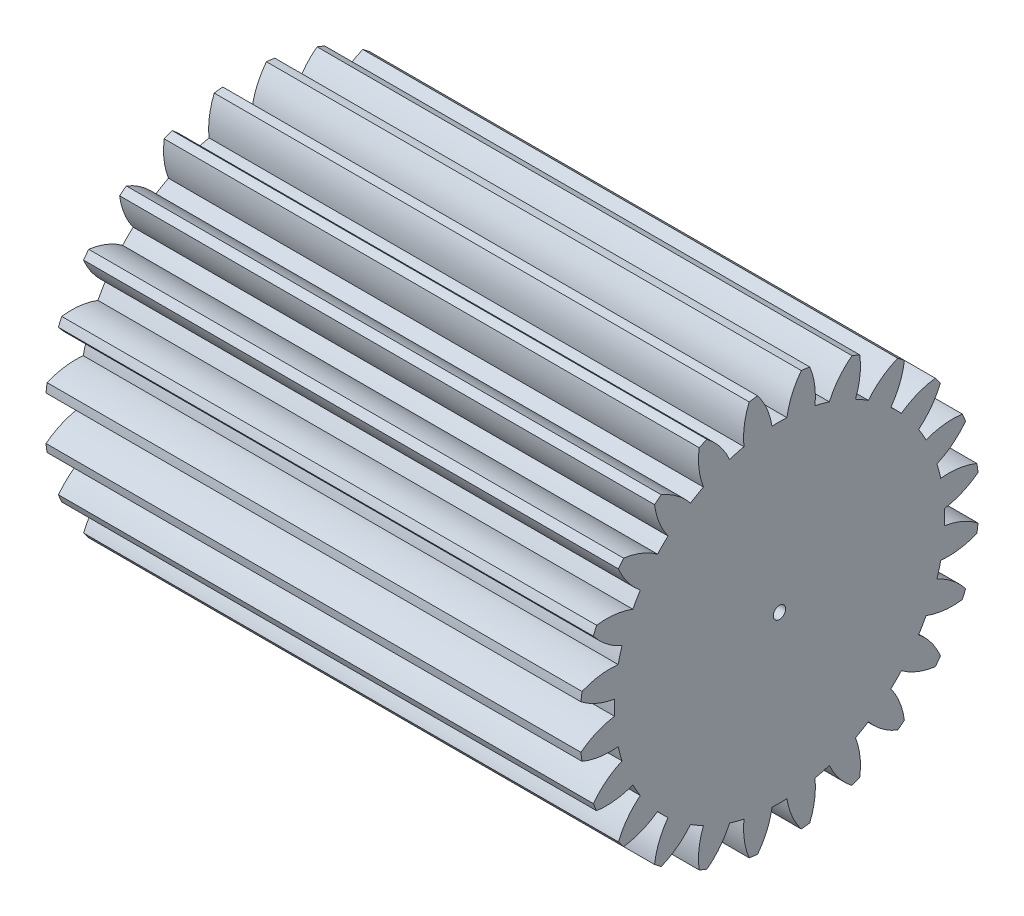
SolidWorks part; units mm, degrees
ref_plane "Plane1" through (0, 0, 0) normal (0, 0, 1) x (1, 0, 0)
ref_plane "Plane2" through (0, 0, 0) normal (0, 1, 0) x (1, 0, 0)
ref_plane "Plane3" through (0, 0, 0) normal (1, 0, 0) x (0, 0, -1)
sketch "HoldingSke" plane through (0, 0, 0) normal (0, 1, 0) x (1, 0, 0)
  line L0 (0, 0) -> (0.9135, -0.4067)
  line L1 (-15, 0) -> (100, 0) construction
  line L2 (0, 0) -> (-2.1039, 2.3779)
  line L3 (0, 0) -> (-11.863, 4.5341)
  line L4 (0, 0) -> (7.8894, 3.5126)
  line L5 (0, 0) -> (-46.8476, -17.4728)
  line L6 (0, 0) -> (-9.9476, -6.7116)
  line L7 (-2.1039, 2.3779) -> (8.6586, 51.2059)
  line L8 (-76.2, 54.61) -> (-76.1, 54.61)
  line L9 (-71.009, 38.7566) -> (-53.1078, 45.2721)
  line L10 (-76.2, 71.12) -> (104.1128, 71.12)
  line L11 (0, 0) -> (-12, 0)
  line L12 (-76.2, 101.6) -> (-76.162, 101.6)
  line L13 (24.9733, 27.94) -> (52.9518, 28.4284)
  line L14 (24.9733, 27.94) -> (24.9743, 27.94)
  line L15 (24.9733, 27.94) -> (100.4006, 29.5858)
  line L16 (-63.627, -1) -> (-12.827, -1)
  circle A0 centre (0, 0) radius 0.4
  circle A1 centre (0, 0) radius 10.749
  circle A2 centre (0, 0) radius 37.5
  circle A3 centre (0, 0) radius 0.4
  dimension "Num_teeth" = 24
  dimension "Pitch_radius" = 180.3128
  dimension "Width" = 12
sketch "BasProSke" plane through (0, 0, 0) normal (0, 1, 0) x (1, 0, 0)
  line L0 (-10, 0) -> (60, 0) construction
  line L1 (0, 0) -> (0, 13)
  line L2 (0, 0) -> (34.815, 0)
  line L3 (34.815, 0) -> (34.815, 13)
  line L4 (34.815, 13) -> (0, 13)
  dimension "Thickness" = 34.815
  dimension "Diameter" = 26
revolve "Base-Revolve" add sketch "BasProSke" angle 360 about L0
sketch "TooCutSke" plane through (0, 0, 0) normal (1, 0, 0) x (0, 0, -1)
  line L1 (0, 0) -> (0, 107) construction
  line L2 (0, 0) -> (-0.8513, 11.9698) construction
  line L3 (0, 0) -> (-3.127, 23.752) construction
  line L4 (-0.8513, 11.9698) -> (-1.5635, 11.876) construction
  arc A0 (0.4834, 10.7381) -> (-0.4834, 10.7381) centre (0, 0) ccw
  arc A1 (1.4409, 12.9455) -> (-1.4409, 12.9455) centre (0, 0) ccw
  circle A2 centre (0, 0) radius 12 construction
  circle A3 centre (0, 0) radius 11.2763 construction
  arc A4 (-0.4834, 10.7381) -> (-1.4409, 12.9455) centre (-5.2252, 9.9926) ccw
  arc A5 (1.4409, 12.9455) -> (0.4834, 10.7381) centre (5.2252, 9.9926) ccw
extrude "ToothCut" cut sketch "TooCutSke" along normal through all
fillet "Breaks" [suppressed] radius 0.02 tangent propagation no
fillet "RootFillets" [suppressed] radius 0.251
pattern_circular "TeethCuts" count 24 every 15 about axis through (-10, 0, 0) along (1, 0, 0) of "ToothCut", "RootFillets", "Breaks"
sketch "HubNeaOneSke" plane through (0, 0, 0) normal (-1, 0, 0) x (0, 0, 1)
  circle A0 centre (0, 0) radius 10.749
  dimension "Diameter" = 21.498
extrude "HubNearOne" [suppressed] add sketch "HubNeaOneSke" along normal blind 15.1851
sketch "HubNeaBotSke" plane through (0, 0, 0) normal (-1, 0, 0) x (0, 0, 1)
  circle A0 centre (0, 0) radius 10.749
  dimension "Diameter" = 21.498
extrude "HubNearBoth" [suppressed] add sketch "HubNeaBotSke" along normal blind 7.5925
ref_plane "FarPln" through (34.815, 0, 0) normal (1, 0, 0) x (0, 0, -1)
sketch "HubFarSke" plane through (34.815, 0, 0) normal (1, 0, 0) x (0, 0, -1)
  circle A0 centre (0, 0) radius 10.749
  dimension "Diameter" = 21.498
extrude "HubFar" [suppressed] add sketch "HubFarSke" along normal blind 7.5925
sketch "BorSke" plane through (0, 0, 0) normal (1, 0, 0) x (0, 0, -1)
  circle A0 centre (0, 0) radius 0.4
  dimension "Diameter" = 0.8
extrude "Bore" cut sketch "BorSke" along normal mid plane 100.0001
sketch "KeySke" plane through (0, 0, 0) normal (1, 0, 0) x (0, 0, -1)
  line L0 (-0.05, 0) -> (-0.05, 0.5)
  line L1 (-0.05, 0.5) -> (0.05, 0.5)
  line L2 (0.05, 0.5) -> (0.05, 0)
  line L3 (0, 0) -> (0, 34) construction
  line L4 (-0.05, 0) -> (0.05, 0)
  dimension "Width" = 0.1
extrude "Keyway" [suppressed] cut sketch "KeySke" along normal mid plane 100.0001
pattern_circular "Keyway2" [suppressed] count 2 every 90 about axis through (-10, 0, 0) along (1, 0, 0) reverse direction yes
scale "Scale1" scale about centroid uniform scaling yes scale factor 2
sketch "Sketch1" plane through (52.2225, 0, 0) normal (1, 0, 0) x (0, 0, -1)
  circle A0 centre (0, 0) radius 23.749 construction
  dimension "D1" = 47.498
equation "' \"Module@HoldingSke\" = 6.35"
equation "' \"Num_teeth@HoldingSke\" = 12"
equation "' \"Ap@HoldingSke\" =  20"
equation "' \"Ap@HoldingSke\" = 20"
equation "' \"Width@HoldingSke\" = 0.5 * 25.4"
equation "' \"Hub_dia@HoldingSke\"= 1 * 25.4"
equation "' \"Hub_dia@HoldingSke\" = 1 * 25.4"
equation "' \"Overall_len@HoldingSke\" = 1.0 * 25.4"
equation "' \"Bore@HoldingSke\" = 0.75 * 25.4"
equation "' \"T_dim@HoldingSke\" = 0.1 * 25.4"
equation "' \"Width@KeySke\" = 0.25 * 25.4"
equation "' \"Show_teeth@HoldingSke\" = 13"
equation "' \"Backlash@HoldingSke\" = 0.009 * 25.4"
equation "' \"Addendum_fac@HoldingSke\" = 1.0"
equation "' \"Dedendum_fac@HoldingSke\" = 1.25"
equation "' \"Dedendum_add@HoldingSke\" = 0.00005 * 25.4"
equation "' \"Clearance_fac@HoldingSke\" = 0.25"
equation "\"Pitch@HoldingSke\" = 1 / \"Module@HoldingSke\""
equation "\"Overcut_dia@TooCutSke\" = (\"Num_teeth@HoldingSke\" + 2 * \"Addendum_fac@HoldingSke\") / \"Pitch@HoldingSke\" + 0.002 * 25.4"
equation "\"Pitch_dia@TooCutSke\" = \"Num_teeth@HoldingSke\" / \"Pitch@HoldingSke\""
equation "\"Base_dia@TooCutSke\" = \"Num_teeth@HoldingSke\" / \"Pitch@HoldingSke\" * cos((\"Ap@HoldingSke\"  * 3.14159265 / 180))"
equation "\"Root_dia@TooCutSke\" = (\"Num_teeth@HoldingSke\" + 2) / \"Pitch@HoldingSke\" - 2 * (\"Addendum_fac@HoldingSke\" + \"Dedendum_fac@HoldingSke\") / \"Pitch@HoldingSke\" - \"Dedendum_add@HoldingSke\" * 2"
equation "\"Half_ang@TooCutSke\" = 180 / \"Num_teeth@HoldingSke\""
equation "\"Half_CT@TooCutSke\" = \"Num_teeth@HoldingSke\" / \"Pitch@HoldingSke\" * sin((3.14159265 / 2 / \"Num_teeth@HoldingSke\")) / 2 - 7 * \"Backlash@HoldingSke\" / 4"
equation "\"Flank_rad@TooCutSke\" = \"Num_teeth@HoldingSke\" / \"Pitch@HoldingSke\" / 5"
equation "\"Radius@RootFillets\" = \"Clearance_fac@HoldingSke\" / \"Pitch@HoldingSke\" + \"Dedendum_add@HoldingSke\""
equation "\"Break_rad@Breaks\" = 0.02 / \"Pitch@HoldingSke\""
equation "\"Thickness@HoldingSke\" = \"Width@HoldingSke\""
equation "\"OAL@HoldingSke\" = \"Thickness@HoldingSke\""
equation "\"MHD@HoldingSke\" = (\"Num_teeth@HoldingSke\" + 2) / \"Pitch@HoldingSke\" - 2 * (\"Addendum_fac@HoldingSke\" + \"Dedendum_fac@HoldingSke\")  / \"Pitch@HoldingSke\" - \"Dedendum_add@HoldingSke\" * 2"
equation "\"MBD@HoldingSke\" = (\"Num_teeth@HoldingSke\" + 2) / \"Pitch@HoldingSke\" - 2 * (\"Addendum_fac@HoldingSke\" + \"Dedendum_fac@HoldingSke\")  / \"Pitch@HoldingSke\" - \"Dedendum_add@HoldingSke\" * 2 - 0.002 * 25.4"
equation "\"MHD@HoldingSke\" = ((sgn( \"MHD@HoldingSke\" - \"Hub_dia@HoldingSke\" )-1)*( \"MHD@HoldingSke\" - \"Hub_dia@HoldingSke\" ))/-2+ \"Hub_dia@HoldingSke\""
equation "\"MBD@HoldingSke\" = ((sgn( \"MBD@HoldingSke\" - \"Bore@HoldingSke\" )-1)*( \"MBD@HoldingSke\" - \"Bore@HoldingSke\" ))/-2+ \"Bore@HoldingSke\""
equation "\"OAL@HoldingSke\" = ((sgn( \"OAL@HoldingSke\" - \"Overall_len@HoldingSke\" )+1)*( \"OAL@HoldingSke\" - \"Overall_len@HoldingSke\" ))/2 + \"Overall_len@HoldingSke\" + 0.000002 * 25.4"
equation "\"Num_teeth@TeethCuts\" = int( \"Show_teeth@HoldingSke\" ) + 1"
equation "\"Num_teeth@TeethCuts\" = ((sgn( \"Num_teeth@TeethCuts\" - \"Num_teeth@HoldingSke\" )-1)*( \"Num_teeth@TeethCuts\" - \"Num_teeth@HoldingSke\" ))/-2+ \"Num_teeth@HoldingSke\""
equation "\"Num_teeth@TeethCuts\" = ((sgn( \"Num_teeth@TeethCuts\" - 2.0)+1)*( \"Num_teeth@TeethCuts\" - 2.0))/2 +2.0"
equation "\"Angle@TeethCuts\" = 360.0 / \"Num_teeth@HoldingSke\""
equation "\"Diameter@BasProSke\" = (\"Num_teeth@HoldingSke\" + 2 * \"Addendum_fac@HoldingSke\") / \"Pitch@HoldingSke\""
equation "' \"Fillet_rad@BasProSke\" =  \"Thickness@HoldingSke\" * 0.05"
equation "' \"Fillet_rad@BasProSke\" = \"Thickness@HoldingSke\" * 0.05"
equation "\"MHD@HoldingSke\" = ((sgn( \"MHD@HoldingSke\" - \"Root_dia@TooCutSke\" )-1)*( \"MHD@HoldingSke\" - \"Root_dia@TooCutSke\" ))/-2+ \"Root_dia@TooCutSke\""
equation "\"Diameter@HubNeaOneSke\" = \"MHD@HoldingSke\""
equation "\"Length@HubNearOne\" = \"OAL@HoldingSke\" - \"Thickness@BasProSke\""
equation "\"Diameter@HubNeaBotSke\" = \"MHD@HoldingSke\""
equation "\"Length@HubNearBoth\" = ( \"OAL@HoldingSke\" - \"Thickness@BasProSke\" ) / 2.0"
equation "\"Thickness@FarPln\" = \"Thickness@BasProSke\""
equation "\"Diameter@HubFarSke\" = \"MHD@HoldingSke\""
equation "\"Length@HubFar\" = ( \"OAL@HoldingSke\" - \"Thickness@BasProSke\" ) / 2.0"
equation "\"Diameter@BorSke\" = \"MBD@HoldingSke\""
equation "\"D1@Bore\" = \"OAL@HoldingSke\" * 2.0"
equation "\"D1@Keyway\" = \"OAL@HoldingSke\" * 2.0"
equation "\"Offset@KeySke\" = \"T_dim@HoldingSke\" + \"MBD@HoldingSke\" / 2.0"
